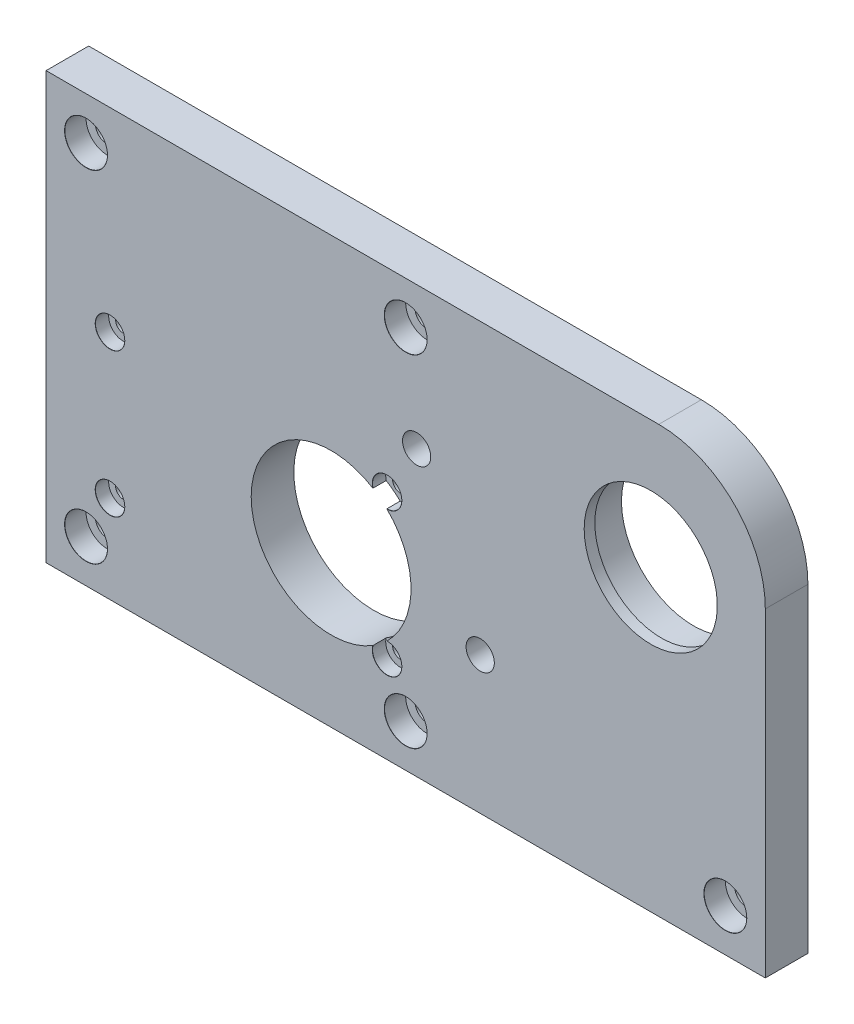
SolidWorks part; units mm, degrees
ref_plane "Front Plane" through (0, 0, 0) normal (0, 0, 1) x (1, 0, 0)
ref_plane "Top Plane" through (0, 0, 0) normal (0, 1, 0) x (1, 0, 0)
ref_plane "Right Plane" through (0, 0, 0) normal (1, 0, 0) x (0, 0, -1)
sketch "Sketch1" plane through (0, 0, 0) normal (0, 0, 1) x (1, 0, 0)
  line L0 (-80.2274, 0) -> (136.4732, 0) construction
  line L1 (0, 62.2135) -> (0, -38.2024) construction
  line L2 (60, 62.2135) -> (60, -38.2024) construction
  line L3 (-53.5, 50) -> (81.5, 50)
  line L4 (-53.5, 50) -> (-53.5, -30)
  line L5 (-53.5, -30) -> (81.5, -30)
  line L6 (81.5, 50) -> (81.5, -30)
  line L7 (14, 62.2135) -> (14, -38.2024) construction
  line L8 (-95.5402, 10) -> (136.4732, 10) construction
  line L9 (10.5, 13.5) -> (-41.5, 13.5) construction
  line L10 (10.5, 13.5) -> (10.5, -13.5) construction
  line L11 (10.5, -13.5) -> (-41.5, -13.5) construction
  line L12 (-41.5, 13.5) -> (-41.5, -13.5) construction
  line L13 (-15.5, 20.6681) -> (-15.5, -19.7942) construction
  line L14 (15.3695, 26) -> (99.374, 26) construction
  line L15 (0, 0) -> (60, 26) construction
  line L16 (16.0768, 23.2606) -> (27.6673, -3.4865) construction
  line L17 (-46, -22) -> (74, -22) construction
  line L18 (-46, -21.2794) -> (-46, 42) construction
  line L19 (-46, 42) -> (14, 42) construction
  line L20 (-64.0714, 10) -> (-27.5649, 10) construction
  circle A0 centre (0, 0) radius 15
  point P20 (60, 0)
  point P26 (60, 26)
  point P30 (27.9854, -4.2208)
  point P31 (16.0572, 23.3059)
  point P34 (-46, -22)
  point P35 (14, -22)
  point P37 (74, -22)
  point P42 (-46, 42)
  point P43 (14, 42)
  dimension "D7" = 30
  dimension "D1" = 60
  dimension "D2" = 135
  dimension "D3" = 80
  dimension "D5" = 67.5
  dimension "D6" = 14
  dimension "D8" = 52
  dimension "D9" = 27
  dimension "D10" = 13.5
  dimension "D4" = 40
  dimension "D12" = 10
  dimension "D13" = 26
  dimension "D11" = 15.5
  dimension "D14" = 10.5
  dimension "D15" = 16
  dimension "D16" = 24
  dimension "D17" = 30
  dimension "D18" = 15
  dimension "D21" = 64
  dimension "D23" = 32
  dimension "D24" = 0
  dimension "D25" = 60
  dimension "D26" = 60
  dimension "D20" = 3
  dimension "D22" = 2
extrude "Boss-Extrude1" add sketch "Sketch1" along normal blind 8
hole_wizard "CBORE for M2.5 SHCS1" positions "Sketch2" profile "Sketch3" counterbore size "M2.5" standard "ANSI Metric" end condition through all
sketch "Sketch2" plane through (0, 0, 8) normal (0, 0, 1) x (1, 0, 0)
  point P0 (10.5, 13.5)
  point P3 (-41.5, 13.5)
  point P6 (-41.5, -13.5)
  point P9 (10.5, -13.5)
sketch "Sketch3" plane through (10.5, 13.5, 8) normal (1, 0, 0) x (0, -1, 0)
  line L0 (0, 0) -> (0, 8)
  line L1 (0, 8) -> (1.45, 8)
  line L3 (1.45, 8) -> (1.45, 2.5)
  line L4 (2.75, 2.5) -> (1.45, 2.5)
  line L5 (2.75, 2.5) -> (2.75, 0.025)
  line L6 (2.75, 0.025) -> (2.775, 0)
  line L7 (2.775, 0) -> (0, 0)
  line L8 (-2.75, 0.025) -> (-2.775, 0) construction
  line L11 (0, -6.35) -> (0, 107.95) construction
  dimension "Thru Hole Dia." = 2.9
  dimension "Thru Hole Depth" = 8
  dimension "C'Bore Dia." = 5.5
  dimension "C'Bore Depth" = 2.5
  dimension "Near C'Sink Dia." = 5.55
  dimension "Near C'Sink Angle" = 90
ref_axis "Axis1" through (0, 0, 0) along (0, 0, 1)
ref_axis "Axis2" through (60, 26, 0) along (0, 0, 1)
ref_plane "Plane1" through (60, 0, 0) normal (1, 0, 0) x (0, 0, -1)
sketch "Sketch4" plane through (60, 0, 0) normal (1, 0, 0) x (0, 0, -1)
  line L0 (-8, 26) -> (0, 26)
  line L1 (0, 39.5) -> (-6, 39.5)
  line L2 (-6, 39.5) -> (-6, 38.5)
  line L3 (-6, 38.5) -> (-8, 38.5)
  line L4 (-8, 38.5) -> (-8, 26)
  line L5 (0, 39.5) -> (0, 26)
  line L6 (0, 26) -> (-22.2295, 26) construction
  line L7 (0, 41.9033) -> (0, 7.5635) construction
  dimension "D1" = 8
  dimension "D2" = 12.5
  dimension "D3" = 13.5
  dimension "D4" = 6
revolve "Cut-Revolve1" cut sketch "Sketch4" angle 360 about axis through (60, 26, 0) along (0, 0, 1)
hole_wizard "M5 Clearance Hole1" positions "Sketch9" profile "Sketch11" hole size "M5" standard "ANSI Metric" end condition through all
sketch "Sketch9" plane through (0, 0, 0) normal (0, 0, -1) x (-1, 0, 0)
  point P0 (-16.0572, 23.3059)
  point P4 (-27.9854, -4.2208)
sketch "Sketch11" plane through (16.0572, 23.3059, 0) normal (1, 0, 0) x (0, 1, 0)
  line L0 (0, 0) -> (0, 8)
  line L1 (0, 8) -> (2.65, 8)
  line L2 (2.65, 8) -> (2.65, 0.025)
  line L3 (2.65, 0.025) -> (2.675, 0)
  line L5 (2.675, 0) -> (0, 0)
  line L6 (-2.65, 0.025) -> (-2.675, 0) construction
  line L11 (0, -6.35) -> (0, 107.95) construction
  dimension "Thru Hole Dia." = 5.3
  dimension "Thru Hole Depth" = 8
  dimension "Near C'Sink Dia." = 5.35
  dimension "Near C'Sink Angle" = 90
hole_wizard "CBORE for M4 SHCS1" positions "Sketch12" profile "Sketch13" counterbore size "M4" standard "ANSI Metric" end condition through all
sketch "Sketch12" plane through (0, 0, 8) normal (0, 0, 1) x (1, 0, 0)
  point P0 (-46, -22)
  point P3 (14, -22)
  point P6 (74, -22)
  point P9 (-46, 42)
  point P12 (14, 42)
sketch "Sketch13" plane through (-46, -22, 8) normal (1, 0, 0) x (0, -1, 0)
  line L0 (0, 0) -> (0, 8)
  line L1 (0, 8) -> (2.25, 8)
  line L3 (2.25, 8) -> (2.25, 4)
  line L4 (4, 4) -> (2.25, 4)
  line L5 (4, 4) -> (4, 0.025)
  line L6 (4, 0.025) -> (4.025, 0)
  line L7 (4.025, 0) -> (0, 0)
  line L8 (-4, 0.025) -> (-4.025, 0) construction
  line L11 (0, -6.35) -> (0, 107.95) construction
  dimension "Thru Hole Dia." = 4.5
  dimension "Thru Hole Depth" = 8
  dimension "C'Bore Dia." = 8
  dimension "C'Bore Depth" = 4
  dimension "Near C'Sink Dia." = 8.05
  dimension "Near C'Sink Angle" = 90
fillet "Fillet1" radius 20 1 edges at (81.5, 50, 4)
equation "\"motor_shaftA_center_center\"=60"
equation "\"motor_shaftA_centerX\"=60"
equation "\"D1@Sketch1\"=\"motor_shaftA_centerX\""
equation "\"plateA_length\"= 135"
equation "\"D2@Sketch1\"=\"plateA_length\""
equation "\"plateA_height\"= 80"
equation "\"D3@Sketch1\"=\"plateA_height\""
equation "\"D5@Sketch1\"=\"plateA_length\"/2"
equation "\"motor_offsetX\"= 14"
equation "\"D6@Sketch1\"=\"motor_offsetX\""
equation "\"plateA_thickness\"= 8"
equation "\"D1@Boss-Extrude1\"=\"plateA_thickness\""
equation "\"plateA_odA\"= 30"
equation "\"D7@Sketch1\"=\"plateA_odA\""
equation "\"motor_bolt_pattern_width\"=52"
equation "\"motor_bolt_pattern_length\"=52"
equation "\"D8@Sketch1\"=\"motor_bolt_pattern_length\""
equation "\"motor_bolt_pattern_height\"=27"
equation "\"D9@Sketch1\"=\"motor_bolt_pattern_height\""
equation "\"D10@Sketch1\"=\"motor_bolt_pattern_height\"/2"
equation "\"shaftA_bearing_od\"= 27"
equation "\"plateA_odC\"=25"
equation "\"plateA_odB\"= 27"
equation "\"shaftA_bearing_depth\"=4"
equation "\"D4@Sketch1\"=\"plateA_height\"/2"
equation "\"plateA_offsetY\"=10"
equation "\"D12@Sketch1\"=\"plateA_offsetY\""
equation "\"D13@Sketch1\"=\"motor_bolt_pattern_length\"/2"
equation "\"motor_bolt_pattern_offset\"=15.5"
equation "\"motor_bolt_pattern_offsetX\"=15.5"
equation "\"D11@Sketch1\"=\"motor_bolt_pattern_offsetX\""
equation "\"plateA_shaftA_offsetY\"=16"
equation "\"D15@Sketch1\"=\"plateA_shaftA_offsetY\""
equation "\"D1@Sketch4\"=\"plateA_thickness\""
equation "\"plateA_idC\"=27"
equation "\"D2@Sketch4\"=\"plateA_idB\"/2"
equation "\"plateA_idB\"=25"
equation "\"D3@Sketch4\"=\"plateA_idC\"/2"
equation "\"plateA_bearing_depth\"=4.46734"
equation "\"plateA_shaftA_bearing_depth\"=6"
equation "\"D4@Sketch4\"=\"plateA_shaftA_bearing_depth\""
equation "\"plateA_bolt_pattern_height\"=64"
equation "\"D21@Sketch1\"=\"plateA_bolt_pattern_height\""
equation "\"D23@Sketch1\"=\"plateA_bolt_pattern_height\"/2"
equation "\"plateA_bolt_pattern_offsetY\"=0"
equation "\"D24@Sketch1\"=\"plateA_bolt_pattern_offsetY\""
equation "\"plateA_bolt_spacingX\"=60"
equation "\"D26@Sketch1\"=\"plateA_bolt_spacingX\""
equation "\"D25@Sketch1\"=\"plateA_bolt_spacingX\""
